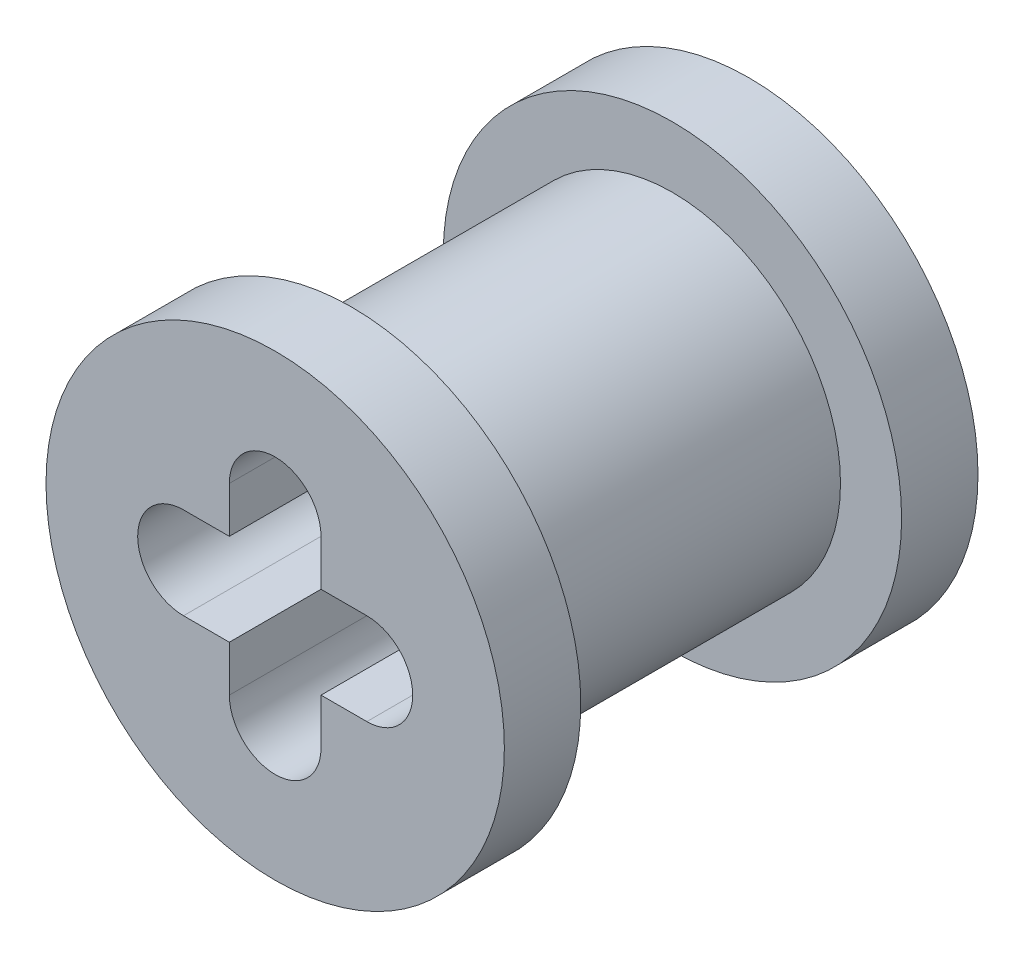
SolidWorks part; units mm, degrees
material "PVC Rigid"
ref_plane "Front Plane" through (0, 0, 0) normal (0, 0, 1) x (1, 0, 0)
ref_plane "Top Plane" through (0, 0, 0) normal (0, 1, 0) x (1, 0, 0)
ref_plane "Right Plane" through (0, 0, 0) normal (1, 0, 0) x (0, 0, -1)
sketch "Sketch1" plane through (0, 0, 0) normal (0, 0, 1) x (1, 0, 0)
  line L0 (-7.874, 0) -> (7.874, 0) construction
  line L1 (6.35, 0) -> (9.398, 0) construction
  line L2 (6.35, 0.762) -> (9.398, 0.762)
  line L10 (6.35, -0.762) -> (9.398, -0.762)
  line L19 (7.874, 1.524) -> (7.874, -1.524) construction
  line L20 (8.636, 1.524) -> (8.636, -1.524)
  line L21 (7.112, 1.524) -> (7.112, -1.524)
  line L22 (6.35, 0) -> (9.398, 0) construction
  circle A0 centre (7.874, 0) radius 2.794
  arc A2 (6.35, 0.762) -> (6.35, -0.762) centre (6.35, 0) ccw
  circle A4 centre (7.874, 0) radius 2.54
  arc A5 (9.398, -0.762) -> (9.398, 0.762) centre (9.398, 0) ccw
  circle A23 centre (7.874, 0) radius 2.286 construction
  arc A24 (8.636, 1.524) -> (7.112, 1.524) centre (7.874, 1.524) ccw
  arc A25 (7.112, -1.524) -> (8.636, -1.524) centre (7.874, -1.524) ccw
  point P13 (9.525, 0)
  point P14 (7.874, 0)
  point P15 (7.62, 0)
  point P17 (0, 3.302)
  point P18 (19.05, 3.302)
  point P19 (0, -3.302)
  point P20 (19.05, -3.302)
  point P23 (13.843, 0)
  point P24 (7.874, 0)
  point P25 (23.368, 0)
  point P26 (3.429, 0)
  point P27 (-7.874, -3.302)
  point P28 (7.874, -3.302)
  point P29 (-7.874, 3.302)
  point P30 (7.874, 3.302)
  point P35 (11.811, 0)
  point P60 (11.5175, 1.1139)
  point P70 (7.874, 0)
  point P77 (7.874, 0)
  dimension "D4" = 5.08
  dimension "D7" = 4.572
  dimension "D8" = 1.524
extrude "Boss-Extrude1" add sketch "Sketch1" along normal blind 3.937 contours A4 | L20 A25 L21 A4 A24 region at (5.159, 0, 0) region at (5.4058, 0, 0)
sketch "Sketch2" plane through (0, 0, 0) normal (0, 0, -1) x (-1, 0, 0)
  circle A0 centre (-7.874, 0) radius 2.794
  circle A1 centre (-7.874, 0) radius 3.81
extrude "Boss-Extrude2" add sketch "Sketch2" against normal blind 1.27
ref_plane "Plane1" through (0, 0, 3.937) normal (0, 0, 1) x (1, 0, 0)
mirror "Mirror1" about plane through (0, 0, 3.937) normal (0, 0, 1) of "Boss-Extrude2", "Boss-Extrude1"
